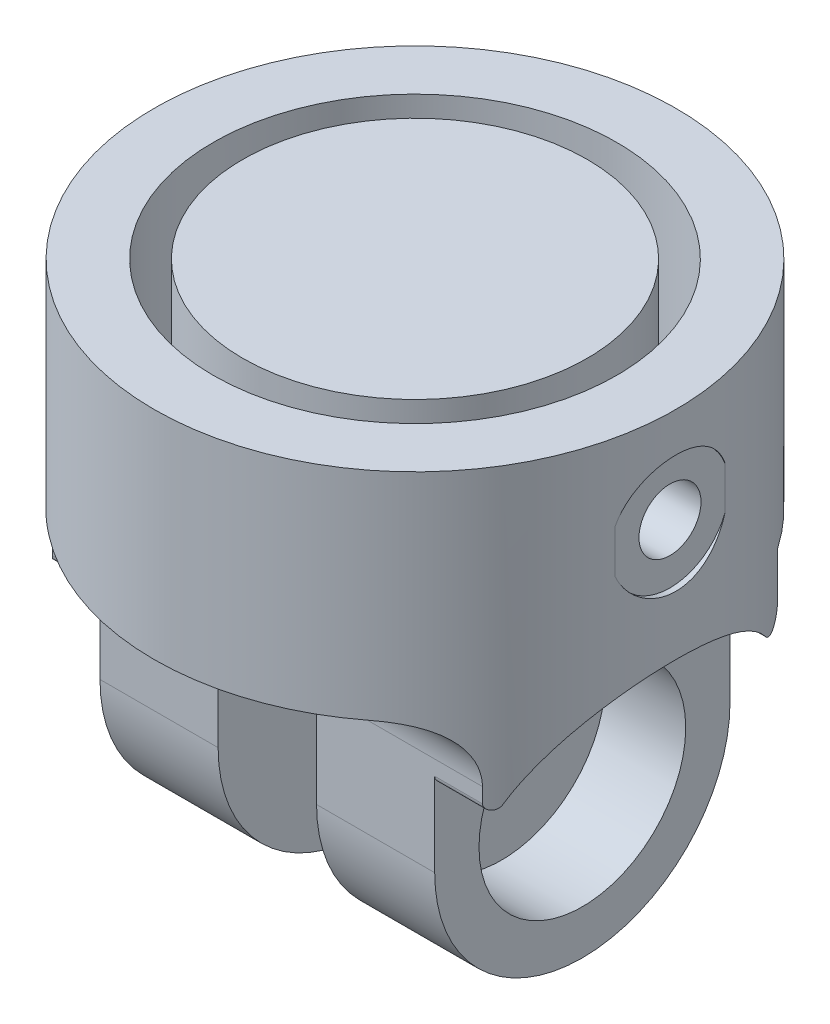
SolidWorks part; units mm, degrees
material "PLA Black"
ref_plane "Front" through (0, 0, 0) normal (0, 0, 1) x (1, 0, 0)
ref_plane "Top" through (0, 0, 0) normal (0, 1, 0) x (1, 0, 0)
ref_plane "Right" through (0, 0, 0) normal (1, 0, 0) x (0, 0, -1)
sketch "Sketch1" plane through (0, 0, 0) normal (0, 1, 0) x (1, 0, 0)
  line L0 (0, 8.75) -> (0, 10.25) construction
  circle A0 centre (0, 0) radius 10.25
  circle A1 centre (0, 0) radius 13.25
  circle A2 centre (0, 0) radius 9.5 construction
  circle A4 centre (0, 0) radius 8.75
  point P11 (0, 9.5)
  dimension "D1" = 1.5
  dimension "D2" = 3
  dimension "D3" = 19
extrude "Boss-Extrude1" add sketch "Sketch1" along normal blind 10 contours A1 A0 | A4 region at (-12.8752, 0, 0) region at (0, 0, 0)
sketch "Sketch3" plane through (0, 0, 0) normal (0, -1, 0) x (1, 0, 0)
  circle A2 centre (0, 0) radius 13.25 construction
  circle A3 centre (0, 0) radius 13.25
extrude "Boss-Extrude2" add sketch "Sketch3" along normal blind 1
sketch "Sketch4" plane through (0, -1, 0) normal (0, -1, 0) x (1, 0, 0)
  line L0 (0, 17.8908) -> (0, -17.0763) construction
  line L1 (2.5, 7.5) -> (8.5, 7.5)
  line L2 (2.5, 7.5) -> (2.5, -7.5)
  line L3 (2.5, -7.5) -> (8.5, -7.5)
  line L4 (8.5, 7.5) -> (8.5, -7.5)
  line L5 (-8.5, 7.5) -> (-8.5, -7.5)
  line L6 (-2.5, -7.5) -> (-8.5, -7.5)
  line L7 (-2.5, 7.5) -> (-2.5, -7.5)
  line L8 (-2.5, 7.5) -> (-8.5, 7.5)
  line L9 (16.8049, 0) -> (-19.8998, 0) construction
  dimension "D1" = 6
  dimension "D2" = 5
  dimension "D3" = 15
extrude "Boss-Extrude3" add sketch "Sketch4" along normal blind 16
sketch "Sketch5" plane through (8.5, 0, 0) normal (1, 0, 0) x (0, 0, -1)
  line L0 (-7.5, -17) -> (-7.5, -1) construction
  line L1 (7.5, -17) -> (7.5, -1) construction
  line L2 (7.5, -9) -> (7.5, -17.1619)
  line L3 (7.5, -17.1619) -> (-7.5, -17.1619)
  line L4 (-7.5, -17.1619) -> (-7.5, -9)
  arc A0 (-7.5, -9) -> (7.5, -9) centre (0, -9) ccw
  circle A1 centre (0, -9) radius 1.75
  dimension "D1" = 3.5
extrude "Cut-Extrude1" cut sketch "Sketch5" against normal through all both and the other way through all
sketch "Sketch6" plane through (8.5, 0, 0) normal (1, 0, 0) x (0, 0, -1)
  circle A0 centre (0, -9) radius 5.25
  dimension "D1" = 10.5
extrude "Cut-Extrude2" cut sketch "Sketch6" against normal blind 4.1
mirror "Mirror1" about plane through (0, 0, 0) normal (1, 0, 0) of "Cut-Extrude2"
ref_plane "Plane9" through (2.25, 0, 0) normal (1, 0, 0) x (0, 0, -1)
sketch "Sketch7" plane through (2.25, 0, 0) normal (1, 0, 0) x (0, 0, -1)
  line L0 (3.6, -9) -> (3.6, -1) construction
  line L1 (7.5, -1) -> (-7.5, -1) construction
  line L2 (3.5026, -8.1681) -> (1.8, -1) construction
  line L3 (3.2149, -7.38) -> (0, -1) construction
  line L4 (1.8, -0.6757) -> (1.8, -1.4422) construction
  line L5 (2.8087, -6.748) -> (-1.8, -1) construction
  line L6 (2.3875, -6.3056) -> (-3.6, -1) construction
  line L8 (0, -1.6788) -> (0, 0) construction
  line L9 (-8.4824, -9) -> (8.712, -9) construction
  line L10 (2.0173, -6.0183) -> (-5.4, -1) construction
  line L11 (-3.6, -0.3587) -> (-3.6, -1.6788) construction
  circle A0 centre (0, -9) radius 3.6 construction
  dimension "D1" = 7.2
  dimension "D2" = 34.081
  dimension "D3" = 8
ref_plane "Plane1" through (2.25, -1, -3.6) normal (0, 1, 0) x (1, 0, 0)
ref_plane "Plane2" through (2.25, -1, -1.8) normal (0, 0.9729, 0.2311) x (1, 0, 0)
ref_plane "Plane3" through (2.25, -1, 0) normal (0, 0.893, 0.45) x (1, 0, 0)
ref_plane "Plane5" through (2.25, -1, 1.8) normal (0, 0.7802, 0.6255) x (1, 0, 0)
ref_plane "Plane6" through (2.25, -1, 3.6) normal (0, 0.6632, 0.7484) x (1, 0, 0)
ref_plane "Plane7" through (2.25, -1, 5.4) normal (0, 0.5604, 0.8282) x (1, 0, 0)
sketch "Sketch8" plane through (2.25, -1, -3.6) normal (0, 1, 0) x (1, 0, 0)
  circle A0 centre (0, 0) radius 0.825
  dimension "D1" = 1.65
extrude "Cut-Extrude5" cut sketch "Sketch8" along normal blind 5.5 and the other way through all
sketch "Sketch9" plane through (2.25, -1, -1.8) normal (0, 0.9729, 0.2311) x (1, 0, 0)
  circle A0 centre (0, 0) radius 0.825
  dimension "D1" = 1.65
extrude "Cut-Extrude3" cut sketch "Sketch9" along normal blind 5.5
sketch "Sketch10" plane through (2.25, -1, 0) normal (0, 0.893, 0.45) x (1, 0, 0)
  circle A0 centre (0, 0) radius 0.825
  dimension "D1" = 1.65
sketch "Sketch11" plane through (2.25, -1, 1.8) normal (0, 0.7802, 0.6255) x (1, 0, 0)
  circle A0 centre (0, 0) radius 0.825
  dimension "D1" = 1.65
sketch "Sketch12" plane through (2.25, -1, 3.6) normal (0, 0.6632, 0.7484) x (1, 0, 0)
  circle A0 centre (0, 0) radius 0.825
  dimension "D1" = 1.65
sketch "Sketch14" plane through (2.25, -1, 5.4) normal (0, 0.5604, 0.8282) x (1, 0, 0)
  circle A0 centre (0, 0) radius 0.825
  dimension "D1" = 1.65
extrude "Cut-Extrude6" cut sketch "Sketch10" along normal blind 5.5 and the other way through all
extrude "Cut-Extrude7" cut sketch "Sketch11" along normal blind 5.5 and the other way through all contours A0
extrude "Cut-Extrude8" cut sketch "Sketch12" along normal blind 5.5 and the other way through all contours A0
extrude "Cut-Extrude9" cut sketch "Sketch14" along normal blind 5.5 and the other way through all contours A0
ref_plane "Plane8" through (13.25, 0, 0) normal (1, 0, 0) x (0, 0, -1)
hole_wizard "Tap Drill for M3 Helicoil1" positions "Sketch17" profile "Sketch18" hole size "M3x0.5" standard "DIN"
sketch "Sketch17" plane through (13.25, 0, 0) normal (1, 0, 0) x (0, 0, -1)
  line L0 (-22.2973, 5) -> (18.0703, 5) construction
  line L4 (0, 12.2732) -> (0, -5.3405) construction
  line L6 (-7.5, -9) -> (-7.5, -1) construction
  line L7 (7.5, -9) -> (7.5, -1) construction
  line L8 (13.25, 10) -> (-13.25, 10) construction
  line L9 (10.25, 0) -> (-10.25, 0) construction
  point P0 (0, 5)
sketch "Sketch18" plane through (13.25, 5, 0) normal (0, 1, 0) x (0, 0, -1)
  line L0 (0, 0) -> (0, 6.9464)
  line L1 (0, 6.9464) -> (1.575, 6)
  line L2 (1.575, 6) -> (1.575, 0)
  line L5 (1.575, 0) -> (0, 0)
  line L10 (0, 6.9464) -> (-1.575, 6) construction
  line L11 (0, -6.35) -> (0, 107.95) construction
  dimension "Hole Dia." = 3.15
  dimension "Hole Depth" = 6
  dimension "Drill Angle" = 118
sketch "Sketch20" plane through (13.25, 0, 0) normal (1, 0, 0) x (0, 0, -1)
  circle A0 centre (0, 5) radius 3
  dimension "D1" = 6
extrude "Cut-Extrude10" cut sketch "Sketch20" against normal blind 0.3
sketch "Sketch21" plane through (8.5, 0, 0) normal (1, 0, 0) x (0, 0, -1)
  line L0 (7.5, -1) -> (-7.5, -1) construction
  line L1 (7.5, -0.1252) -> (7.5, -3.188)
  line L2 (0.9244, -19.5662) -> (-4.8209, -14.7453) construction
  line L3 (0, 5.2718) -> (0, -9.2894) construction
  line L4 (0, 10) -> (0, -1) construction
  line L5 (-7.5, -0.1252) -> (-7.5, -4.7575)
  line L6 (7.5, -0.1252) -> (-7.5, -0.1252)
  line L7 (-7.5, -9) -> (-7.5, -1) construction
  line L8 (7.5, -9) -> (7.5, -1) construction
  line L9 (0, -1) -> (9.1102, -5.2607) construction
  line L10 (0, -1) -> (1.2641, -0.2702) construction
  line L11 (6.0277, -3.7401) -> (7.5, -3.188) construction
  line L12 (10.5662, -8.0756) -> (4.8209, -3.2547) construction
  line L13 (-4.8209, -14.7453) -> (4.8209, -3.2547) construction
  line L14 (10.5662, -8.0756) -> (0.9244, -19.5662) construction
  arc A0 (-6.8849, -4.9259) -> (6.0277, -3.7401) centre (0, -9) cw
  arc A1 (-6.8849, -4.9259) -> (-7.5, -4.7575) centre (-7.1694, -4.7575) cw
  arc A2 (7.5, -3.188) -> (6.0277, -3.7401) centre (6.6603, -3.188) cw
  circle A3 centre (0, -9) radius 1.75 construction
  arc A4 (-4.8209, -14.7453) -> (4.8209, -3.2547) centre (0, -9) cw construction
  dimension "D1" = 30
  dimension "D3" = 7.5
  dimension "D2" = 50
  dimension "D4" = 15
extrude "Boss-Extrude4" add sketch "Sketch21" along normal up to surface (2.423 mm away) up to face at (13.0965, 5, 0)
mirror "Mirror2" about plane through (0, 0, 0) normal (1, 0, 0) of "Boss-Extrude4", "Tap Drill for M3 Helicoil1", "Cut-Extrude10"
fillet "Fillet1" radius 3 2 edges at (-6.7115, -1, 7.5) (6.7115, -1, 7.5)
equation "\"knee_angle\"= 70"
equation "\"ankle_angle\" = 70"
equation "\"hip_angle\" = 30"
equation "\"spring_ankle_parallel_arm_diameter\"= 1.5"
equation "\"spring_ankle_parallel_arm_length\"= 13"
equation "\"spring_ankle_parallel_intern_diameter\"= 5.7"
equation "\"spring_ankle_parallel_angle\"= \"ankle_angle\""
equation "\"spring_ankle_parallel_turns\"= 3"
equation "\"spring_ankle_parallel_pitch\"= \"spring_ankle_parallel_arm_diameter\" * 1.01"
equation "\"spring_ankle_parallel_cutting_distance\"= (1-\"spring_ankle_parallel_angle\" / 360) * \"spring_ankle_parallel_pitch\""
equation "\"spring_ankle_serial_arm_diameter\"= 1.91"
equation "\"spring_ankle_serial_arm_length\"= 10"
equation "\"spring_ankle_serial_intern_diameter\"= 5.7"
equation "\"spring_ankle_serial_angle\"= \"90\""
equation "\"spring_ankle_serial_turns\"= 3"
equation "\"spring_ankle_serial_pitch\"= \"spring_ankle_serial_arm_diameter\" * 1.01"
equation "\"spring_ankle_serial_cutting_distance\"= (1-\"spring_ankle_serial_angle\" / 360) * \"spring_ankle_serial_pitch\""
equation "\"spring_knee_parallel_arm_diameter\"= 1.5"
equation "\"spring_knee_parallel_arm_length\"= 13"
equation "\"spring_knee_parallel_intern_diameter\"= 5.7"
equation "\"spring_knee_parallel_angle\"= -\"knee_angle\" + 90"
equation "\"spring_knee_parallel_turns\"= 3"
equation "\"spring_knee_parallel_pitch\"= \"spring_knee_parallel_arm_diameter\" * 1.01"
equation "\"spring_knee_parallel_cutting_distance\"= (1-(\"spring_knee_parallel_angle\") / 360) * \"spring_knee_parallel_pitch\""
equation "\"spring_knee_serial_arm_diameter\"= 1.91"
equation "\"spring_knee_serial_arm_length\"= 10"
equation "\"spring_knee_serial_intern_diameter\"= 5.7"
equation "\"spring_knee_serial_angle\"= \"90\""
equation "\"spring_knee_serial_turns\"= 3"
equation "\"spring_knee_serial_pitch\"= \"spring_knee_serial_arm_diameter\" * 1.01"
equation "\"spring_knee_serial_cutting_distance\"= (1-\"spring_knee_serial_angle\" / 360) * \"spring_knee_serial_pitch\""
equation "\"spring_ankle_parallel_nominal_diameter\"= \"spring_ankle_parallel_arm_diameter\" + \"spring_ankle_parallel_intern_diameter\""
equation "\"spring_ankle_serial_nominal_diameter\"= \"spring_ankle_serial_arm_diameter\" + \"spring_ankle_serial_intern_diameter\""
equation "\"spring_knee_parallel_nominal_diameter\"= \"spring_knee_parallel_arm_diameter\" + \"spring_knee_parallel_intern_diameter\""
equation "\"spring_knee_serial_nominal_diameter\"= \"spring_knee_serial_arm_diameter\" + \"spring_knee_serial_intern_diameter\""
equation "\"D1@Sketch7\"=\"spring_ankle_parallel_nominal_diameter\""
equation "\"D1@Sketch8\"=\"spring_ankle_parallel_arm_diameter\"*1.1"
equation "\"D1@Sketch9\"=\"spring_ankle_parallel_arm_diameter\"*1.1"
equation "\"D1@Sketch10\"=\"spring_ankle_parallel_arm_diameter\"*1.1"
equation "\"D1@Sketch11\"=\"spring_ankle_parallel_arm_diameter\"*1.1"
equation "\"D1@Sketch12\"=\"spring_ankle_parallel_arm_diameter\"*1.1"
equation "\"D1@Sketch14\"=\"spring_ankle_parallel_arm_diameter\"*1.1"
equation "\"D1@Cut-Extrude3\"=\"spring_ankle_parallel_arm_length\"-\"axis_structure_distance\""
equation "\"axis_structure_distance\"= 7.5"
equation "\"D1@Cut-Extrude5\"=\"spring_ankle_parallel_arm_length\"-\"axis_structure_distance\""
equation "\"D1@Cut-Extrude6\"=\"spring_ankle_parallel_arm_length\"-\"axis_structure_distance\""
equation "\"D1@Cut-Extrude7\"=\"spring_ankle_parallel_arm_length\"-\"axis_structure_distance\""
equation "\"D1@Cut-Extrude8\"=\"spring_ankle_parallel_arm_length\"-\"axis_structure_distance\""
equation "\"D1@Cut-Extrude9\"=\"spring_ankle_parallel_arm_length\"-\"axis_structure_distance\""
equation "\"D1@Boss-Extrude3\"=\"axis_structure_distance\"*2"
equation "\"ankle_angle_max\" = 120"
equation "\"ankle_angle_min\" = 50"
equation "\"knee_angle_max\" = 120"
equation "\"knee_angle_min\" = 0"
equation "\"hip_angle_max\" = 90"
equation "\"hip_angle_min\" = -60"
equation "\"D1@Sketch21\"=\"ankle_angle_max\"-90"
equation "\"D2@Sketch21\"=\"ankle_angle_min\""
equation "\"D1@Plane9\"=(\"spring_ankle_parallel_arm_diameter\"*\"spring_ankle_parallel_turns\")/2"
